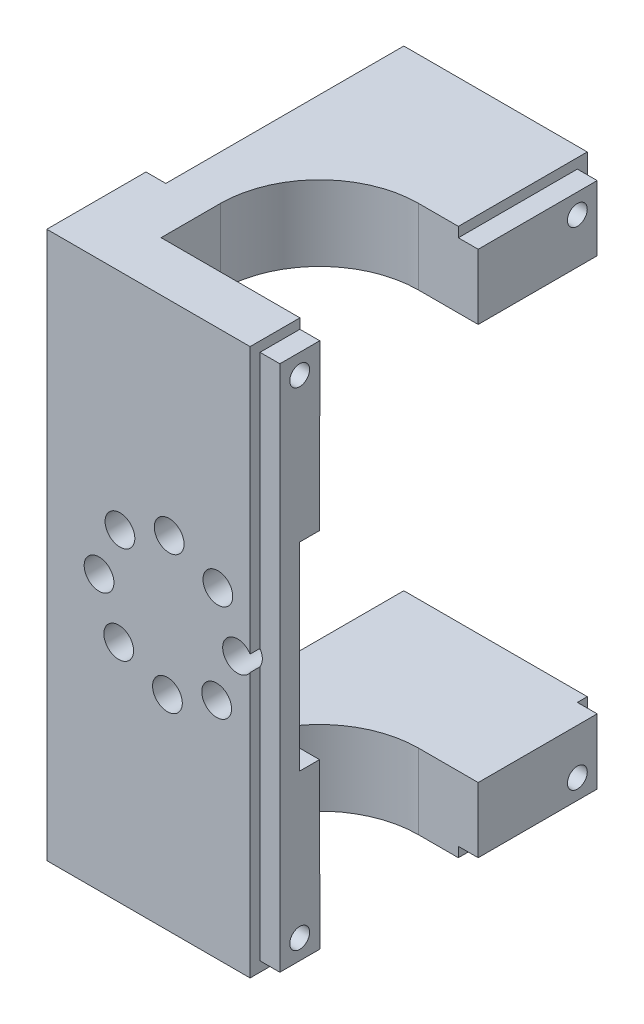
SolidWorks part; units mm, degrees
ref_plane "前视基准面" through (0, 0, 0) normal (0, 0, 1) x (1, 0, 0)
ref_plane "上视基准面" through (0, 0, 0) normal (0, 1, 0) x (1, 0, 0)
ref_plane "右视基准面" through (0, 0, 0) normal (1, 0, 0) x (0, 0, -1)
other "Configuration Table"
sketch "草图1" plane through (0, 0, 0) normal (0, 0, 1) x (1, 0, 0)
  line L0 (-1000, 0) -> (49000, 0) construction
  line L1 (-10.25, -20) -> (10.25, -20)
  line L2 (-10.25, -20) -> (-10.25, 20)
  line L3 (-10.25, 20) -> (10.25, 20)
  line L4 (10.25, -20) -> (10.25, 20)
  line L5 (-10.25, -20) -> (10.25, 20) construction
  line L6 (-10.25, 20) -> (10.25, -20) construction
  line L7 (-5, 15) -> (5, 15)
  line L8 (-5, 15) -> (-5, 25)
  line L9 (-5, 25) -> (5, 25)
  line L10 (5, 15) -> (5, 25)
  line L11 (-5, 15) -> (5, 25) construction
  line L12 (-5, 25) -> (5, 15) construction
  line L14 (-10.25, -35.1417) -> (10.25, -35.1417)
  line L15 (-10.25, -35.1417) -> (-10.25, 35.1417)
  line L16 (-10.25, 35.1417) -> (10.25, 35.1417)
  line L17 (10.25, -35.1417) -> (10.25, 35.1417)
  line L18 (-10.25, -35.1417) -> (10.25, 35.1417) construction
  line L19 (-10.25, 35.1417) -> (10.25, -35.1417) construction
  circle A0 centre (-5, 25) radius 2
  circle A1 centre (5, 25) radius 2
  circle A2 centre (5, -25) radius 2
  circle A3 centre (-5, -25) radius 2
  point P0 (0, 0)
  point P6 (0, 20)
  point P19 (0, 0)
  dimension "D5" = 4
  dimension "D6" = 4
  dimension "D1" = 20.5
  dimension "D2" = 40
  dimension "D3" = 10
  dimension "D4" = 10
extrude "凸台-拉伸1" add sketch "草图1" along normal blind 29 contours A1 L10 L3 L17 L16 L15 L8 A0 L9 | L14 L17 L1 L15 A2 A3 | A1 L9 A0 L8 L3 L10 region at (0, -27.7973, 0) region at (0, 28.799, 0) region at (0, 22.2627, 0)
sketch "草图2" plane through (0, 0, 29) normal (0, 0, 1) x (1, 0, 0)
  line L1 (-10.25, 35.1417) -> (10.25, 35.1417)
  line L2 (-10.25, 35.1417) -> (-10.25, -35.1417)
  line L3 (-10.25, -35.1417) -> (10.25, -35.1417)
  line L4 (10.25, 35.1417) -> (10.25, -35.1417)
extrude "凸台-拉伸2" add sketch "草图2" along normal blind 3
sketch "草图3" plane through (0, 0, 0) normal (0, 0, -1) x (-1, 0, 0)
  line L0 (-10.25, -35.1417) -> (-10.25, -20) construction
  line L1 (-10.25, -27.5709) -> (10.25, -27.5709)
  line L2 (-10.25, -27.5709) -> (-10.25, 27.5709)
  line L3 (-10.25, 27.5709) -> (10.25, 27.5709)
  line L4 (10.25, -27.5709) -> (10.25, 27.5709)
  line L5 (10.25, 20) -> (10.25, 35.1417) construction
  line L7 (-10.25, -35.1417) -> (10.25, -35.1417)
  line L8 (-10.25, -35.1417) -> (-10.25, 35.1417)
  line L9 (-10.25, 35.1417) -> (10.25, 35.1417)
  line L10 (10.25, -35.1417) -> (10.25, 35.1417)
  line M2 (-10.25, -35.1417) -> (10.25, -35.1417)
  line M3 (10.25, -35.1417) -> (10.25, -20)
  line M5 (-10.25, -20) -> (-10.25, -35.1417)
extrude "切除-拉伸1" cut sketch "草图3" against normal through all contours L1 M5 M2 M3 | L3 L10 L9 L8 region at (0, -31.3563, 0) region at (0, 31.3563, 0)
sketch "草图5" plane through (0, -27.5709, 0) normal (0, -1, 0) x (1, 0, 0)
  line L0 (0, 0) -> (0, 2.5)
  circle A0 centre (0, 2.5) radius 2.5
  dimension "D2" = 5
  dimension "D1" = 2.5
extrude "凸台-拉伸3" add sketch "草图5" along normal blind 10 contours A0 region at (1.7178, -27.5709, 0.7822)
sketch "草图8" plane through (0, 27.5709, 0) normal (0, 1, 0) x (1, 0, 0)
  line L0 (0, 0) -> (0, -2.5)
  line L1 (0, -2.5) -> (0, -16.5)
  line L2 (0, -16.5) -> (0, -26.5)
  circle A0 centre (0, -16.5) radius 1.6
  circle A1 centre (0, -26.5) radius 1.6
  dimension "D4" = 3.2
  dimension "D5" = 3.2
  dimension "D1" = 2.5
  dimension "D2" = 14
  dimension "D3" = 10
extrude "切除-拉伸2" cut sketch "草图8" against normal up to next contours L1 A0 L2 | L2 A0 L1 | A1 region at (0.6791, 27.5709, 16.5) region at (1.0994, 27.5709, 25.4006) region at (-0.6791, 27.5709, 16.5)
sketch "草图9" plane through (0, -27.5709, 0) normal (0, -1, 0) x (1, 0, 0)
  line L1 (-10.25, 32) -> (10.25, 32)
  line L2 (-10.25, 32) -> (-10.25, 0)
  line L3 (-10.25, 0) -> (10.25, 0)
  line L4 (10.25, 32) -> (10.25, 0)
extrude "切除-拉伸3" cut sketch "草图9" along normal through all
sketch "草图12" plane through (0, 0, 0) normal (0, 0, -1) x (-1, 0, 0)
  line L1 (-10.25, 27.5709) -> (10.25, 27.5709)
  line L2 (-10.25, 27.5709) -> (-10.25, 20)
  line L3 (-10.25, 20) -> (10.25, 20)
  line L4 (10.25, 27.5709) -> (10.25, 20)
  circle A0 centre (-5, 25) radius 2
  circle A1 centre (5, 25) radius 2
extrude "凸台-拉伸5" add sketch "草图12" against normal blind 30
sketch "草图13" plane through (0, 27.5709, 0) normal (0, 1, 0) x (1, 0, 0)
  line L0 (0, 0) -> (0, -32)
  line L1 (10.25, -32) -> (-10.25, -32) construction
  line L2 (0, 0) -> (0, -10)
  line L3 (0, 0) -> (0, -2.5275)
  line L4 (0, 0) -> (0, -5)
  circle A2 centre (0, -5) radius 2.5
  circle A3 centre (0, -5) radius 4
  dimension "D3" = 5
  dimension "D4" = 5
  dimension "D5" = 8
  dimension "D1" = 32
  dimension "D2" = 10
extrude "凸台-拉伸6" add sketch "草图13" along normal blind 10 contours L4 A3 L2 A2 | L2 A3 L4 A2 region at (-2.5894, 27.5709, 5) region at (0.0894, 27.5709, 1.75)
sketch "草图15" plane through (0, 0, 0) normal (1, 0, 0) x (0, 0, -1)
  line L0 (-1, 27.5709) -> (0, 27.5709)
  line L1 (-1, 27.5709) -> (-1, 28.676)
  line L2 (-1, 27.5709) -> (-1, 37.5709) construction
  line L3 (-5, -962.4291) -> (-5, 49037.5709) construction
  line L4 (-2.5, 37.5709) -> (-7.5, 37.5709) construction
  arc A0 (-1, 28.676) -> (0, 27.5709) centre (0.1107, 28.676) ccw
  point P13 (-5, 37.5709)
revolve "旋转1" add sketch "草图15" angle 360 about L3
ref_plane "基准面1" through (0, 0, 5) normal (0, 0, 1) x (1, 0, 0)
sketch "草图16" plane through (0, 0, 5) normal (0, 0, 1) x (1, 0, 0)
  line L0 (0, 37.5709) -> (0, 33.5709)
  line L1 (2.5, 37.5709) -> (-2.5, 37.5709) construction
  circle A0 centre (0, 33.5709) radius 1.5
  dimension "D2" = 3
  dimension "D1" = 4
extrude "切除-拉伸5" cut sketch "草图16" against normal through all contours A0 region at (-1.0307, 32.5402, 5)
sketch "草图17" plane through (0, 0, 0) normal (1, 0, 0) x (0, 0, -1)
  line L0 (-5, 37.5709) -> (-5, 33.5709)
  line L1 (-2.5, 37.5709) -> (-7.5, 37.5709) construction
  line L2 (-5, 11.275) -> (-5, -11.275) construction
  circle A0 centre (-5, 33.5709) radius 1.5
  dimension "D2" = 3
  dimension "D1" = 4
extrude "切除-拉伸6" cut sketch "草图17" against normal through all contours A0 region at (0, 32.5402, 6.0307)
sketch "草图19" plane through (0, -27.5709, 0) normal (0, -1, 0) x (1, 0, 0)
  line L0 (0, 0) -> (0, 5)
  line L1 (10.25, 0) -> (-10.25, 0) construction
  circle A0 centre (0, 5) radius 2.5
  circle A1 centre (0, 5) radius 4
  dimension "D2" = 5
  dimension "D3" = 8
  dimension "D1" = 5
extrude "凸台-拉伸7" add sketch "草图19" along normal blind 10 contours A1 A0 region at (-2.7484, -27.5709, 7.7484)
sketch "草图20" plane through (0, 0, 0) normal (1, 0, 0) x (0, 0, -1)
  line L0 (-1, -27.5709) -> (0, -27.5709)
  line L1 (-1, -27.5709) -> (-1, -28.5709)
  line L2 (-1, -37.5709) -> (-1, -27.5709) construction
  line L3 (-5, -1027.5709) -> (-5, 48972.4291) construction
  line L4 (-9, -27.5709) -> (-1, -27.5709) construction
  arc A0 (-1, -28.5709) -> (0, -27.5709) centre (0, -28.5709) cw
  point P13 (-5, -27.5709)
  dimension "D1" = 1
revolve "旋转2" add sketch "草图20" angle 360 about L3
sketch "草图21" plane through (0, 0, 5) normal (0, 0, 1) x (1, 0, 0)
  line L0 (0, -37.5709) -> (0, -33.5709)
  line L1 (-4, -37.5709) -> (4, -37.5709) construction
  circle A0 centre (0, -33.5709) radius 1.5
  dimension "D2" = 3
  dimension "D1" = 4
extrude "切除-拉伸7" cut sketch "草图21" against normal through all contours A0 region at (1.0307, -34.6015, 5)
sketch "草图22" plane through (0, 0, 0) normal (1, 0, 0) x (0, 0, -1)
  line L0 (-5, -37.5709) -> (-5, -33.5709)
  line L1 (-9, -37.5709) -> (-1, -37.5709) construction
  line L2 (-5, 11.275) -> (-5, -11.275) construction
  circle A0 centre (-5, -33.5709) radius 1.5
  dimension "D2" = 3
  dimension "D1" = 4
extrude "切除-拉伸8" cut sketch "草图22" against normal through all contours A0 region at (0, -34.6015, 3.9693)
sketch "草图23" plane through (0, 0, 32) normal (0, 0, 1) x (1, 0, 0)
  line L1 (-10.25, 27.5709) -> (10.25, 27.5709)
  line L2 (-10.25, 27.5709) -> (-10.25, -27.5709)
  line L3 (-10.25, -27.5709) -> (10.25, -27.5709)
  line L4 (10.25, 27.5709) -> (10.25, -27.5709)
extrude "凸台-拉伸8" add sketch "草图23" along normal blind 2
sketch "草图24" plane through (-10.25, 0, 0) normal (-1, 0, 0) x (0, 0, 1)
  line L0 (34, -27.5709) -> (0, -27.5709) construction
  line L1 (34, 27.5709) -> (24, 27.5709)
  line L2 (34, 27.5709) -> (34, -27.5709)
  line L3 (34, -27.5709) -> (24, -27.5709)
  line L4 (24, 27.5709) -> (24, -27.5709)
  dimension "D1" = 10
extrude "凸台-拉伸9" add sketch "草图24" along normal blind 2
sketch "草图25" plane through (10.25, 0, 0) normal (1, 0, 0) x (0, 0, -1)
  line L0 (-34, 27.5709) -> (-21, 27.5709)
  line L1 (-34, 27.5709) -> (0, 27.5709) construction
  line L2 (-21, 27.5709) -> (-17, 27.5709)
  line L3 (-17, 27.5709) -> (-17, -27.5709)
  line L6 (-17, -27.5709) -> (-25, -27.5709)
  line L7 (-34, -27.5709) -> (0, -27.5709) construction
  line L8 (-25, -27.5709) -> (-25, 27.5709)
  line M5 (-29, 20) -> (0, 20)
  line M7 (0, 27.5709) -> (-34, 27.5709)
  line M9 (-34, -27.5709) -> (0, -27.5709)
  line M11 (0, -20) -> (-29, -20)
  dimension "D1" = 13
  dimension "D2" = 4
  dimension "D3" = 8
extrude "切除-拉伸9" cut sketch "草图25" against normal blind 16 contours L8 L3 M9 M11 | L8 L3 M5 M7 region at (10.25, 23.7854, 21) region at (10.25, -23.7854, 21)
sketch "草图26" plane through (0, 0, 29) normal (0, 0, -1) x (-1, 0, 0)
  circle A0 centre (-5, 25) radius 2
  circle A1 centre (5, 25) radius 2
  circle A2 centre (-5, -25) radius 2
  circle A3 centre (5, -25) radius 2
extrude "凸台-拉伸10" add sketch "草图26" along normal blind 20
sketch "草图27" plane through (0, -27.5709, 0) normal (0, -1, 0) x (1, 0, 0)
  line L1 (-5.75, 25) -> (10.25, 25)
  line L2 (-5.75, 25) -> (-5.75, 17)
  line L3 (-5.75, 17) -> (10.25, 17)
  line L4 (10.25, 25) -> (10.25, 17)
extrude "切除-拉伸10" cut sketch "草图27" against normal through all
sketch "草图29" plane through (10.25, 0, 0) normal (1, 0, 0) x (0, 0, -1)
  line L0 (-33, 26.5709) -> (-33, -26.5709)
  line L1 (-34, 27.5709) -> (0, 27.5709)
  line L2 (-34, 27.5709) -> (-34, -27.5709)
  line L3 (-34, -27.5709) -> (0, -27.5709)
  line L4 (0, 27.5709) -> (0, -27.5709)
  line L5 (-33, -26.5709) -> (-1, -26.5709)
  line L6 (-1, 26.5709) -> (-1, -26.5709)
  line L7 (-33, 26.5709) -> (-1, 26.5709)
  dimension "D1" = 1
extrude "切除-拉伸11" cut sketch "草图29" against normal blind 2
sketch "草图30" plane through (10.25, 0, 0) normal (1, 0, 0) x (0, 0, -1)
  line L1 (-34, 27.5709) -> (0, 27.5709)
  line L2 (-34, 27.5709) -> (-34, -27.5709)
  line L3 (-34, -27.5709) -> (0, -27.5709)
  line L4 (0, 27.5709) -> (0, -27.5709)
  dimension "D1" = 34
  dimension "D2" = 55.1417
sketch "草图32" plane through (10.25, 0, 0) normal (1, 0, 0) x (0, 0, -1)
  line L0 (-17, -26.5709) -> (-1, -26.5709) construction
  line L1 (-33, 26.5709) -> (-13, 26.5709)
  line L2 (-33, 26.5709) -> (-33, -26.5709)
  line L3 (-33, -26.5709) -> (-13, -26.5709)
  line L4 (-13, 26.5709) -> (-13, -26.5709)
  line L6 (-13, 26.5709) -> (-28.9769, 26.5709)
  line L7 (-13, 26.5709) -> (-13, -26.5709)
  line L8 (-13, -26.5709) -> (-28.9769, -26.5709)
  line L9 (-28.9769, 26.5709) -> (-28.9769, -26.5709)
  line L10 (-13, -26.5709) -> (-28.9769, -26.5709)
  line L11 (-13, -26.5709) -> (-13, 27.5939)
  line L12 (-13, 27.5939) -> (-28.9769, 27.5939)
  line L13 (-28.9769, -26.5709) -> (-28.9769, 27.5939)
  line L14 (-28.9769, 27.5939) -> (-13, 27.5939)
  line L15 (-28.9769, 27.5939) -> (-28.9769, -27.5919)
  line L16 (-28.9769, -27.5919) -> (-13, -27.5919)
  line L17 (-13, 27.5939) -> (-13, -27.5919)
  line M2 (-25, 26.5709) -> (-33, 26.5709)
  line M5 (-25, -26.5709) -> (-25, -20)
  line M6 (-25, -20) -> (-29, -20)
  line M8 (-29, 20) -> (-25, 20)
  line M9 (-25, 20) -> (-25, 26.5709)
  dimension "D1" = 20
extrude "切除-拉伸13" cut sketch "草图32" against normal blind 16 contours L9 L3 L4 L1 M8 M6 M5 M9 | L9 M2 M8 M9 | L9 L3 M6 M5 | L17 L3 L15 L16 | L13 L1 L11 L12 M2 region at (10.25, 27.0824, 20.9884) region at (10.25, 23.2854, 26.9884) region at (10.25, 0, 20.5949) region at (10.25, -23.2854, 26.9884) region at (10.25, -27.0814, 20.9884)
sketch "草图33" plane through (10.25, 0, 0) normal (1, 0, 0) x (0, 0, -1)
  line L1 (-33, 26.5709) -> (-31, 26.5709)
  line L2 (-33, 26.5709) -> (-33, 24.5709)
  line L3 (-33, 24.5709) -> (-31, 24.5709)
  line L4 (-31, 26.5709) -> (-31, 24.5709)
  line L5 (-33, -26.5709) -> (-31, -26.5709)
  line L6 (-33, -26.5709) -> (-33, -24.5709)
  line L7 (-33, -24.5709) -> (-31, -24.5709)
  line L8 (-31, -26.5709) -> (-31, -24.5709)
  circle A0 centre (-31, 24.5709) radius 1
  circle A1 centre (-31, -24.5709) radius 1
  dimension "D3" = 2
  dimension "D6" = 2
  dimension "D1" = 2
  dimension "D2" = 2
  dimension "D4" = 2
  dimension "D5" = 2
extrude "切除-拉伸14" cut sketch "草图33" against normal blind 16 contours A1 | A0
sketch "草图35" plane through (10.25, 0, 0) normal (1, 0, 0) x (0, 0, -1)
  line L1 (-1, 26.5709) -> (-3, 26.5709)
  line L2 (-1, 26.5709) -> (-1, 24.5709)
  line L3 (-1, 24.5709) -> (-3, 24.5709)
  line L4 (-3, 26.5709) -> (-3, 24.5709)
  line L5 (-1, -26.5709) -> (-3, -26.5709)
  line L6 (-1, -26.5709) -> (-1, -24.5709)
  line L7 (-1, -24.5709) -> (-3, -24.5709)
  line L8 (-3, -26.5709) -> (-3, -24.5709)
  circle A0 centre (-3, 24.5709) radius 1
  circle A1 centre (-3, -24.5709) radius 1
  dimension "D3" = 2
  dimension "D6" = 2
  dimension "D1" = 2
  dimension "D2" = 2
  dimension "D4" = 2
  dimension "D5" = 2
extrude "切除-拉伸15" cut sketch "草图35" against normal blind 5 contours A1 | A0
sketch "草图36" plane through (0, -37.5709, 0) normal (0, -1, 0) x (1, 0, 0)
  circle A1 centre (0, 5) radius 2.65
  dimension "D1" = 5.3
extrude "切除-拉伸16" cut sketch "草图36" against normal blind 10
sketch "草图37" plane through (0, 37.5709, 0) normal (0, 1, 0) x (1, 0, 0)
  circle A0 centre (0, -5) radius 2.65
  dimension "D1" = 5.3
extrude "切除-拉伸17" cut sketch "草图37" against normal blind 10
sketch "草图38" plane through (0, 0, 29) normal (0, 0, -1) x (-1, 0, 0)
  line L0 (-10.25, 27.5709) -> (-10.25, -27.5709) construction
  line L1 (12.25, 27.5709) -> (-10.25, 27.5709)
  line L2 (12.25, 27.5709) -> (12.25, -27.5709)
  line L3 (12.25, -27.5709) -> (-10.25, -27.5709)
  line L4 (-10.25, 27.5709) -> (-10.25, -27.5709)
  line L5 (-10.25, 27.5709) -> (-10.25, -27.5709) construction
  line L7 (-67.737, 75.4855) -> (54.9645, 75.4855)
  line L8 (-67.737, 75.4855) -> (-67.737, -71.4355)
  line L9 (-67.737, -71.4355) -> (54.9645, -71.4355)
  line L10 (54.9645, 75.4855) -> (54.9645, -71.4355)
extrude "切除-拉伸18" cut sketch "草图38" along normal through all
sketch "草图39" plane through (0, 0, 29) normal (0, 0, -1) x (-1, 0, 0)
  line L1 (-5, -5) -> (5, -5)
  line L2 (-5, -5) -> (-5, 5)
  line L3 (-5, 5) -> (5, 5)
  line L4 (5, -5) -> (5, 5)
  line L5 (-5, -5) -> (5, 5) construction
  line L6 (-5, 5) -> (5, -5) construction
  circle A0 centre (0, 0) radius 4
  circle A1 centre (-5, 4.876) radius 1.5
  circle A2 centre (4.876, 5) radius 1.5
  circle A3 centre (5, -4.876) radius 1.5
  circle A4 centre (-4.876, -5) radius 1.5
  circle A5 centre (-0.0877, 6.9834) radius 1.5
  circle A6 centre (4.876, 5) radius 1.5
  circle A7 centre (6.9834, 0.0877) radius 1.5
  circle A8 centre (5, -4.876) radius 1.5
  circle A9 centre (0.0877, -6.9834) radius 1.5
  circle A10 centre (-4.876, -5) radius 1.5
  circle A11 centre (-6.9834, -0.0877) radius 1.5
  point P0 (0, 0)
  point P19 (0, 0)
  point P34 (0, 0)
  dimension "D3" = 8
  dimension "D4" = 3
  dimension "D1" = 10
  dimension "D2" = 10
  dimension "D5" = 4
  dimension "D6" = 8
extrude "切除-拉伸22" cut sketch "草图39" against normal blind 5 contours A7 | A9 | A11 | A1 | A5 | A2 | A3 | A4 region at (-6.9834, 0.0877, 29) region at (-0.0877, -6.9834, 29) region at (6.9834, -0.0877, 29)
sketch "草图41" plane through (0, 0, 29) normal (0, 0, -1) x (-1, 0, 0)
  line L0 (-10.25, 27.5709) -> (-10.25, -27.5709) construction
  line L1 (10.25, -10) -> (-10.25, -10)
  line L2 (10.25, -10) -> (10.25, 10)
  line L3 (10.25, 10) -> (-10.25, 10)
  line L4 (-10.25, -10) -> (-10.25, 10)
  line L5 (10.25, -10) -> (-10.25, 10) construction
  line L6 (10.25, 10) -> (-10.25, -10) construction
  point P0 (0, 0)
  dimension "D1" = 20
extrude "切除-拉伸23" cut sketch "草图41" against normal blind 2
fillet "圆角1" radius 10 1 edges at (-5.75, 23.7854, 13) type face fillet first side face at (4.25, 24.7139, 13) second side face at (-5.75, 23.7854, 20.9884)
fillet "圆角2" radius 10 1 edges at (-5.75, -23.7854, 13) type face fillet first side face at (-5.75, -23.7854, 20.9884) second side face at (4.25, -24.7139, 13)
